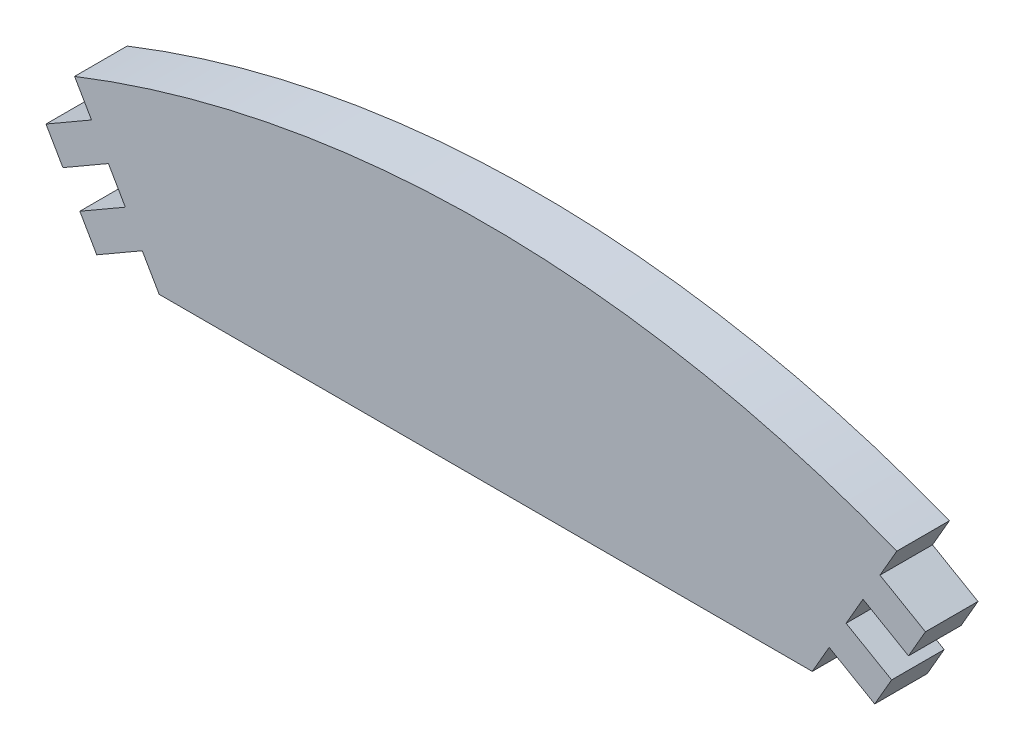
SolidWorks part; units mm, degrees
ref_plane "Front Plane" through (0, 0, 0) normal (0, 0, 1) x (1, 0, 0)
ref_plane "Top Plane" through (0, 0, 0) normal (0, 1, 0) x (1, 0, 0)
ref_plane "Right Plane" through (0, 0, 0) normal (1, 0, 0) x (0, 0, -1)
sketch "Sketch1" plane through (0, 0, 0) normal (0, 0, 1) x (1, 0, 0)
  line L1 (-32, 88) -> (32, 88)
  line L2 (-38.6309, 99.4851) -> (-40.2886, 102.3564)
  line L3 (0, 88) -> (0, 136.6413) construction
  line L5 (32, 88) -> (33.6577, 90.8713)
  line L6 (33.6577, 90.8713) -> (38.1178, 88.2963)
  line L7 (38.1178, 88.2963) -> (39.7755, 91.1675)
  line L8 (39.7755, 91.1675) -> (35.3155, 93.7425)
  line L9 (35.3155, 93.7425) -> (36.9732, 96.6138)
  line L10 (36.9732, 96.6138) -> (41.4332, 94.0388)
  line L11 (41.4332, 94.0388) -> (43.091, 96.9101)
  line L12 (43.091, 96.9101) -> (38.6309, 99.4851)
  line L13 (38.6309, 99.4851) -> (40.2886, 102.3564)
  line L14 (-43.091, 96.9101) -> (-38.6309, 99.4851)
  line L15 (-41.4332, 94.0388) -> (-43.091, 96.9101)
  line L16 (-36.9732, 96.6138) -> (-41.4332, 94.0388)
  line L17 (-35.3155, 93.7425) -> (-36.9732, 96.6138)
  line L18 (-39.7755, 91.1675) -> (-35.3155, 93.7425)
  line L19 (-38.1178, 88.2963) -> (-39.7755, 91.1675)
  line L20 (-33.6577, 90.8713) -> (-38.1178, 88.2963)
  line L21 (-32, 88) -> (-33.6577, 90.8713)
  arc A0 (-40.2886, 102.3564) -> (40.2886, 102.3564) centre (0, 0) cw
  point P12 (0, 110)
  dimension "D1" = 110
  dimension "D2" = 22
  dimension "D3" = 120
  dimension "D4" = 64
  dimension "D5" = 5.15
extrude "Boss-Extrude1" add sketch "Sketch1" along normal blind 5.15
